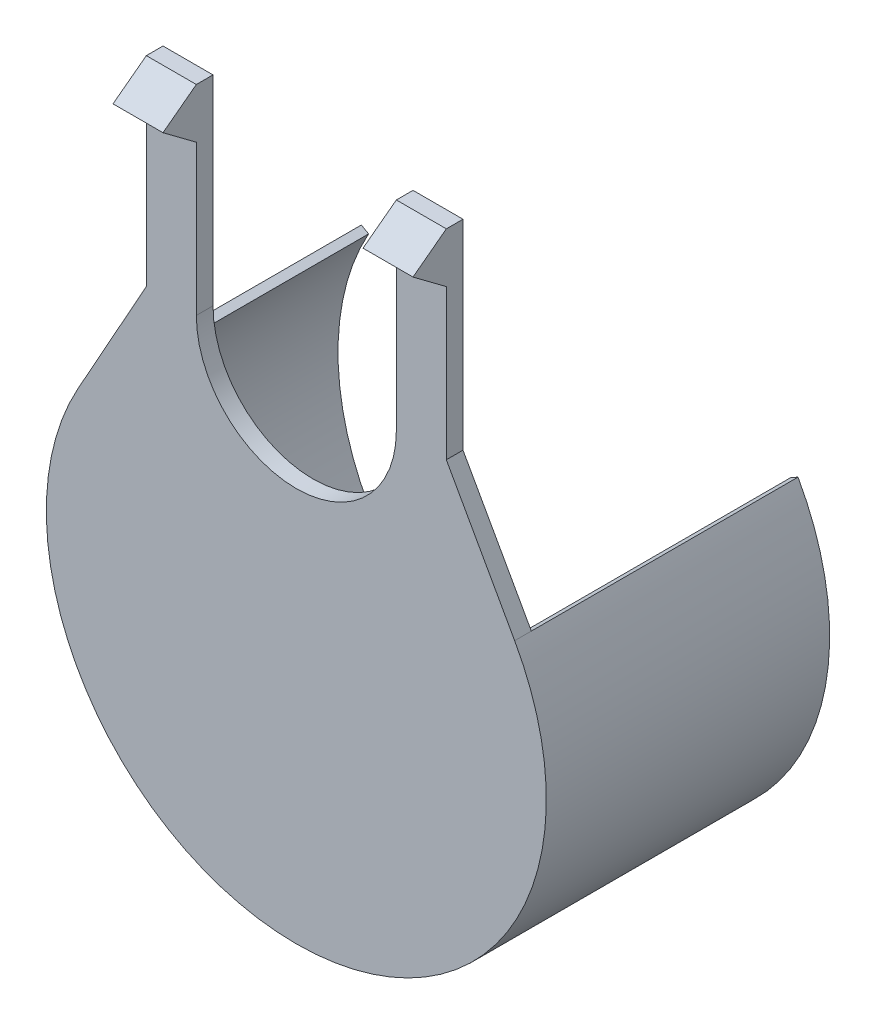
SolidWorks part; units mm, degrees
ref_plane "정면" through (0, 0, 0) normal (0, 0, 1) x (1, 0, 0)
ref_plane "윗면" through (0, 0, 0) normal (0, 1, 0) x (1, 0, 0)
ref_plane "우측면" through (0, 0, 0) normal (1, 0, 0) x (0, 0, -1)
sketch "스케치1" plane through (0, 0, 0) normal (0, 0, 1) x (1, 0, 0)
  line L0 (0, 77.7793) -> (0, -30) construction
  line L2 (-45, 0) -> (-45, 60)
  line L3 (-45, 60) -> (-30, 60)
  line L4 (-30, 0) -> (-30, 60)
  line L5 (30, 0) -> (30, 60)
  line L6 (45, 60) -> (30, 60)
  line L7 (45, 0) -> (45, 60)
  line L9 (-45, 0) -> (-65.5002, -36.754)
  line L10 (45, 0) -> (65.5002, -36.754)
  arc A1 (-30, 0) -> (30, 0) centre (0, 0) ccw
  arc A2 (-65.5002, -36.754) -> (65.5002, -36.754) centre (0, -73.2879) ccw
  dimension "D4" = 150
  dimension "D1" = 15
  dimension "D2" = 60
  dimension "D3" = 30
extrude "보스-돌출1" add sketch "스케치1" along normal blind 5
sketch "스케치2" plane through (0, 0, 0) normal (0, 0, -1) x (-1, 0, 0)
  line L0 (-65.5002, -36.754) -> (-63.3168, -37.9718)
  line L1 (63.3168, -37.9718) -> (65.5002, -36.754)
  arc A0 (-65.5002, -36.754) -> (65.5002, -36.754) centre (0, -73.2879) ccw
  arc A1 (-65.5002, -36.754) -> (65.5002, -36.754) centre (0, -73.2879) ccw construction
  arc A2 (-63.3168, -37.9718) -> (63.3168, -37.9718) centre (0, -73.2879) ccw
  dimension "D1" = 145
extrude "보스-돌출2" add sketch "스케치2" along normal blind 80
sketch "스케치3" plane through (45, 0, 0) normal (1, 0, 0) x (0, 0, -1)
  line L0 (-5, 60) -> (-15, 52.4734)
  line L1 (-15, 52.4734) -> (-5, 45)
  line L2 (-5, 0) -> (-5, 60) construction
  line L3 (-5, 60) -> (-5, 45)
  dimension "D1" = 10
  dimension "D2" = 15
extrude "보스-돌출3" add sketch "스케치3" against normal blind 15
fillet "필렛2" radius 3 1 edges at (0, -145.7879, 0)
mirror "대칭 복사2" about plane through (0, 0, 0) normal (1, 0, 0) of "보스-돌출3"
